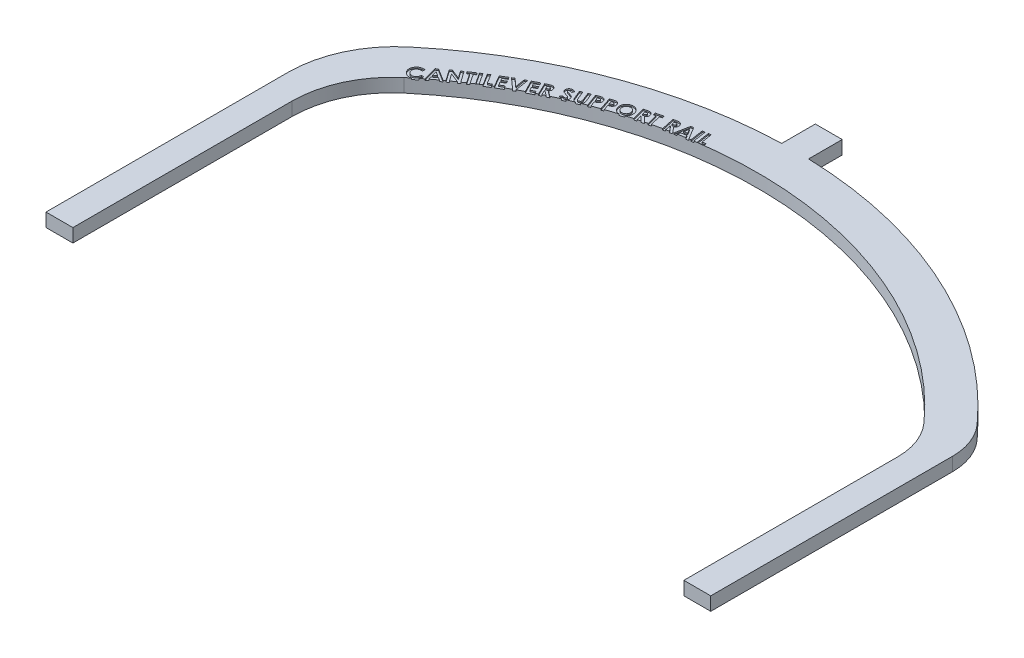
SolidWorks part; units mm, degrees
ref_plane "Front Plane" through (0, 0, 0) normal (0, 0, 1) x (1, 0, 0)
ref_plane "Top Plane" through (0, 0, 0) normal (0, 1, 0) x (1, 0, 0)
ref_plane "Right Plane" through (0, 0, 0) normal (1, 0, 0) x (0, 0, -1)
sketch "Sketch1" plane through (0, 0, 0) normal (0, 1, 0) x (1, 0, 0)
  line L2 (2414.5412, 381.9663) -> (2414.5412, 279.8321) construction
  line L3 (2401.8412, 798.3327) -> (2401.8412, 830.0827)
  line L4 (2401.8412, 830.0827) -> (2427.2412, 830.0827)
  line L5 (2427.2412, 830.0827) -> (2427.2412, 798.3327)
  line L6 (2146.7816, 701.0698) -> (2169.6391, 673.8293) construction
  line L7 (2110.4888, 394.6397) -> (2135.8888, 394.6397)
  line L8 (2110.4888, 394.6397) -> (2110.4888, 623.2397)
  line L10 (2135.8888, 394.6397) -> (2135.8888, 601.4515)
  line L12 (2713.085, 596.772) -> (2713.085, 394.6397)
  line L13 (2713.085, 394.6397) -> (2738.485, 394.6397)
  line L14 (2738.485, 623.2397) -> (2738.485, 394.6397)
  line L15 (2724.1056, 660.6994) -> (2697.6794, 636.9051) construction
  arc A0 (2146.7816, 701.0698) -> (2401.8412, 798.3327) centre (2414.5412, 381.9663) cw
  arc A1 (2169.6391, 673.8293) -> (2697.6794, 636.9051) centre (2414.5412, 381.9663) cw
  arc A2 (2427.2412, 798.3327) -> (2724.1056, 660.6994) centre (2414.5412, 381.9663) cw
  arc A3 (2146.7816, 701.0698) -> (2110.4888, 623.2397) centre (2212.0888, 623.2397) ccw
  arc A4 (2169.6391, 673.8293) -> (2135.8888, 601.4515) centre (2230.3713, 601.4515) ccw
  arc A5 (2697.6794, 636.9051) -> (2713.085, 596.772) centre (2653.1071, 596.772) cw
  arc A6 (2724.1056, 660.6994) -> (2738.485, 623.2397) centre (2682.5024, 623.2397) cw
  circle A7 centre (2363.7412, 379.4263) radius 60.7995 construction
  dimension "D1" = 381
  dimension "D4" = 101.6
  dimension "D2" = 35.56
  dimension "D3" = 228.6
  dimension "D5" = 25.4
  dimension "D6" = 31.75
  dimension "D7" = 40
  dimension "D8" = 48
  dimension "D9" = 50.8
  dimension "D10" = 2.54
  dimension "D11" = 25.4
  dimension "D12" = 25.4
extrude "Boss-Extrude1" add sketch "Sketch1" along normal blind 12.7
sketch "Sketch2" plane through (0, 12.7, 0) normal (0, 1, 0) x (1, 0, 0)
  text T0 "CANTILEVER SUPPORT RAIL" font "Century Gothic" height 12.7
extrude "Cut-Extrude1" cut sketch "Sketch2" against normal blind 1.27
